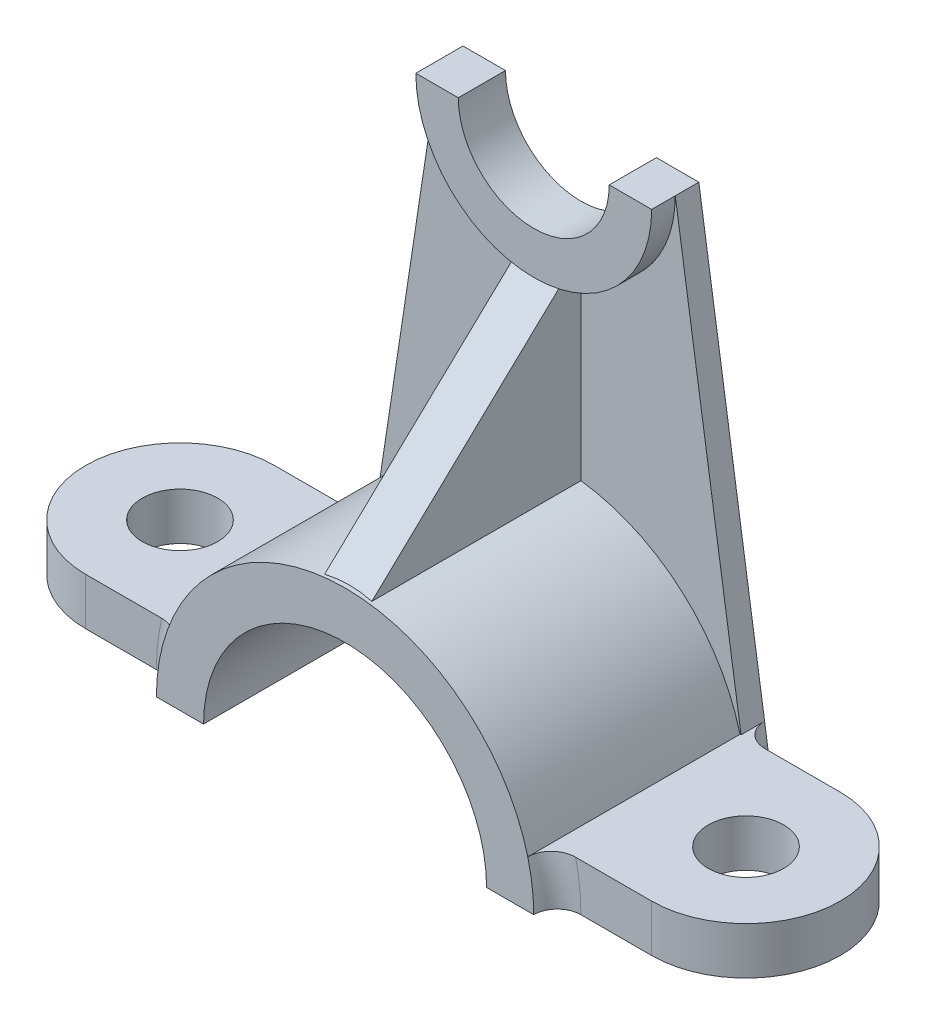
SolidWorks part; units mm, degrees
ref_plane "Front Plane" through (0, 0, 0) normal (0, 0, 1) x (1, 0, 0)
ref_plane "Top Plane" through (0, 0, 0) normal (0, 1, 0) x (1, 0, 0)
ref_plane "Right Plane" through (0, 0, 0) normal (1, 0, 0) x (0, 0, -1)
sketch "Sketch1" plane through (0, 0, 0) normal (0, 0, 1) x (1, 0, 0)
  arc A0 (40, 0) -> (-40, 0) centre (0, 0) ccw
  dimension "D1" = 40
extrude "Extrude-Thin1" add sketch "Sketch1" along normal blind 50 thin thin type one direction reverse wall 10
sketch "Sketch2" plane through (0, 0, 0) normal (0, 0, 1) x (1, 0, 0)
  line L0 (-30, 0) -> (-40, 0) construction
  line L1 (40, 0) -> (30, 0) construction
  line L2 (-30, 0) -> (-40, 0)
  line L3 (40, 0) -> (30, 0)
  line L4 (25, 102) -> (39.5485, 5.993)
  line L5 (-25, 102) -> (-39.5485, 5.993)
  arc A0 (-25, 102) -> (25, 102) centre (0, 102) ccw
  arc A1 (30, 0) -> (-30, 0) centre (0, 0) ccw construction
  arc A2 (40, 0) -> (-40, 0) centre (0, 0) ccw construction
  arc A3 (30, 0) -> (-30, 0) centre (0, 0) ccw
  arc A4 (40, 0) -> (39.5485, 5.993) centre (0, 0) ccw
  arc A5 (-39.5485, 5.993) -> (-40, 0) centre (0, 0) ccw
  dimension "D1" = 25
  dimension "D2" = 102
extrude "Boss-Extrude1" add sketch "Sketch2" along normal blind 5
sketch "Sketch3" plane through (0, 0, 5) normal (0, 0, 1) x (1, 0, 0)
  line L0 (39.5485, 5.993) -> (25, 102) construction
  arc A0 (-25, 102) -> (25, 102) centre (0, 102) ccw
  point P6 (0, 0)
  point P7 (0, 0)
extrude "Extrude-Thin3" add sketch "Sketch3" along normal blind 5 and the other way up to surface (5 mm away) thin contours A0 other way up to face at (0, 27.6254, 0) thin type one direction reverse wall 9
sketch "Sketch4" plane through (0, 0, 0) normal (1, 0, 0) x (0, 0, -1)
  line L0 (-5, 40) -> (-50, 40) construction
  line L1 (-10, 77) -> (-49, 40)
  point P0 (-10, 77)
  point P1 (-49, 40)
  dimension "D1" = 1
rib "Rib6" sketch "Sketch4" sketch "Sketch4" thickness 10 extrusion direction parallel to sketch draft on no parameters "D1"=10
sketch "Sketch5" plane through (0, 0, 0) normal (0, 1, 0) x (1, 0, 0)
  line L0 (30, -50) -> (30, 0) construction
  line L1 (30, -45) -> (80, -45)
  line L2 (30, -45) -> (30, -5)
  line L3 (30, -5) -> (80, -5)
  line L4 (80, -45) -> (80, -5)
  line L5 (-40, -50) -> (40, -50) construction
  dimension "D1" = 5
  dimension "D2" = 40
  dimension "D3" = 80
extrude "Boss-Extrude2" add sketch "Sketch5" along normal blind 10
fillet "Fillet1" 2 edges at (80, 5, 45) (80, 5, 5) type full round first side face at (59.7615, 5.01, 45) second side face at (55.7205, 5.2003, 5) middle face at (80, 5, 25)
sketch "Sketch6" plane through (0, 10, 0) normal (0, 1, 0) x (1, 0, 0)
  circle A0 centre (60, -25) radius 8
  arc A1 (60, -45) -> (60, -5) centre (60, -25) ccw construction
  dimension "D1" = 16
extrude "Cut-Extrude1" cut sketch "Sketch6" against normal through all
fillet "Fillet2" radius 5 3 edges at (39.2449, 7.9965, 5) (39.887, 3.005, 5) (39.6812, 5.0402, 45)
mirror "Mirror1" about plane through (0, 0, 0) normal (1, 0, 0) of "Boss-Extrude2", "Fillet1", "Cut-Extrude1", "Fillet2"
